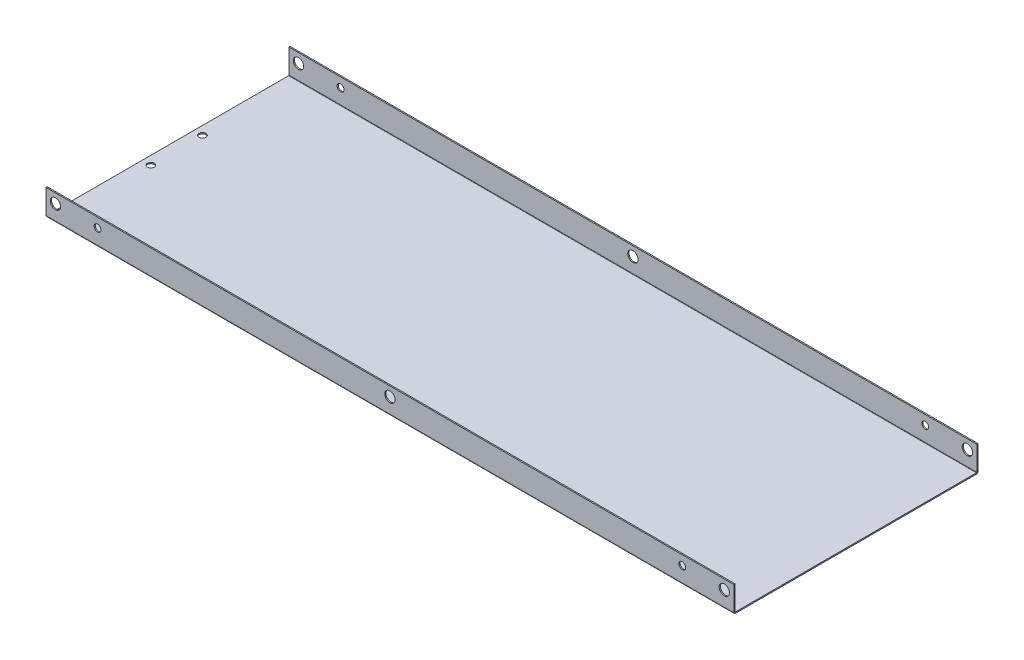
SolidWorks part; units mm, degrees
note: The reader was unsure of these and kept them because the rebuilt part matched: thickness of "基体-法兰1", "边线-法兰1", "钣金8", "钣金9", "钣金10", "钣金11", "钣金12", "钣金13", "钣金14"; flange length of "边线-法兰1".
ref_plane "前视基准面" through (0, 0, 0) normal (0, 0, 1) x (1, 0, 0)
ref_plane "上视基准面" through (0, 0, 0) normal (0, 1, 0) x (1, 0, 0)
ref_plane "右视基准面" through (0, 0, 0) normal (1, 0, 0) x (0, 0, -1)
sketch "草图1" plane through (0, 0, 0) normal (0, 1, 0) x (1, 0, 0)
  line L1 (-200, -71) -> (200, -71)
  line L2 (-200, -71) -> (-200, 71)
  line L3 (-200, 71) -> (200, 71)
  line L4 (200, -71) -> (200, 71)
  line L5 (-200, -71) -> (200, 71) construction
  line L6 (-200, 71) -> (200, -71) construction
  point P0 (0, 0)
  dimension "D1" = 142
  dimension "D2" = 400
base flange "基体-法兰1" sketch "草图1" thickness 0.7 reverse thickness direction no parameters "D1"=0.2
edge flange "边线-法兰1" sketch "草图15" flange profiles "草图15", "草图16" flange angle 90 flange length 15 flange position material inside bend radius 0.2 thickness 0.7 relief rectangular parameters "D6"=10, "D8"=1
sketch "草图15" plane through (0, 0, -71) normal (0, 0, -1) x (-1, 0, 0)
  line L2 (-200, 0) -> (-200, 14.3)
  line L3 (-200, 14.3) -> (200, 14.3)
  line L4 (200, 14.3) -> (200, 0)
  line L11 (-200, 0) -> (200, 0) construction
  line L12 (-200, 0) -> (200, 0)
sketch "草图16" plane through (0, 0, 71) normal (0, 0, 1) x (1, 0, 0)
  line L2 (-200, 0) -> (-200, 14.3)
  line L3 (-200, 14.3) -> (200, 14.3)
  line L4 (200, 14.3) -> (200, 0)
  line L7 (-200, 0) -> (200, 0) construction
  line L8 (-200, 0) -> (200, 0)
bend "边线折弯1" bend radius 0.2 bend angle 90 parameters "D5"=1
bend "边线折弯2" bend radius 0.2 bend angle 90 parameters "D5"=2
sketch "草图17" plane through (0, 0, -71) normal (0, 0, -1) x (-1, 0, 0)
  line L0 (200, 14.3) -> (-200, 14.3) construction
  line L1 (-200, 14.3) -> (-200, 0.2) construction
  line L2 (0, 14.3) -> (0, 0) construction
  circle A0 centre (-194.5, 8.8) radius 3
  circle A1 centre (0, 8.8) radius 3
  circle A2 centre (194.5, 8.8) radius 3
  dimension "D1" = 5.5
  dimension "D2" = 5.5
  dimension "D3" = 6
  dimension "D4" = 5.5
  dimension "D5" = 6
extrude "切除-拉伸1" cut sketch "草图17" against normal blind 10
sketch "草图18" plane through (0, 0, 71) normal (0, 0, 1) x (1, 0, 0)
  line L0 (200, 14.3) -> (-200, 14.3) construction
  line L1 (-200, 14.3) -> (-200, 0.2) construction
  line L2 (0, 14.3) -> (0, 0) construction
  circle A0 centre (-194.5, 8.8) radius 3
  circle A1 centre (0, 8.8) radius 3
  circle A2 centre (194.5, 8.8) radius 3
  dimension "D1" = 5.5
  dimension "D2" = 5.5
  dimension "D3" = 5.5
  dimension "D4" = 6
  dimension "D5" = 6
extrude "切除-拉伸2" cut sketch "草图18" against normal blind 10
sketch "草图19" plane through (0, 0, -71) normal (0, 0, -1) x (-1, 0, 0)
  line L0 (-200, 14.3) -> (-200, 0.2) construction
  line L1 (200, 14.3) -> (-200, 14.3) construction
  line L2 (0, 14.3) -> (0, 0) construction
  circle A0 centre (-170, 8.8) radius 2
  circle A1 centre (170, 8.8) radius 2
  dimension "D2" = 4
  dimension "D3" = 5.5
  dimension "D1" = 30
extrude "切除-拉伸3" cut sketch "草图19" against normal blind 10
sketch "草图20" plane through (0, 0, 71) normal (0, 0, 1) x (1, 0, 0)
  line L0 (-200, 14.3) -> (-200, 0.2) construction
  line L1 (200, 14.3) -> (-200, 14.3) construction
  line L2 (0, 14.3) -> (0, 0) construction
  circle A0 centre (-170, 8.8) radius 2
  circle A1 centre (170, 8.8) radius 2
  dimension "D2" = 4
  dimension "D1" = 30
  dimension "D3" = 5.5
extrude "切除-拉伸4" cut sketch "草图20" against normal blind 10
sketch "草图21" plane through (0, 0, 0) normal (0, 1, 0) x (1, 0, 0)
  line L0 (-200, 0) -> (200, 0) construction
  line L1 (-200, -71) -> (-200, 71) construction
  line L2 (200, -70.1) -> (200, 70.1) construction
  line L3 (-200, 70.1) -> (-200, -70.1) construction
  circle A0 centre (-195, 15) radius 2
  circle A1 centre (-195, -15) radius 2
  dimension "D1" = 4
  dimension "D2" = 15
  dimension "D3" = 5
extrude "切除-拉伸5" cut sketch "草图21" against normal blind 10
sketch "折弯-线3" plane through (0, 0, 0) normal (0, 1, 0) x (1, 0, 0)
sketch "边界框3" plane through (0, 0, 0) normal (0, 1, 0) x (1, 0, 0)
sheet metal parameters "钣金8" thickness 0.7 parameters "D1"=0.2
flat pattern "平板型式8" [suppressed]
sketch "折弯-线4" plane through (0, 0, 0) normal (0, 1, 0) x (1, 0, 0)
sketch "边界框4" [suppressed] plane through (0, 0, 0) normal (0, 1, 0) x (1, 0, 0)
sheet metal parameters "钣金9" thickness 0.7 parameters "D1"=0.2, "D7"=0.01
flat pattern "平板型式8" [suppressed]
sketch "折弯-线4" plane through (0, 0, 0) normal (0, 1, 0) x (1, 0, 0)
sketch "边界框4" [suppressed] plane through (0, 0, 0) normal (0, 1, 0) x (1, 0, 0)
bend of the flat pattern "展平-<边线折弯1>1"
bend of the flat pattern "展平-<边线折弯2>1"
sheet metal parameters "钣金10" thickness 0.7 parameters "D1"=0.2, "D7"=0.01
flat pattern "平板型式8" [suppressed]
sketch "折弯-线4" plane through (0, 0, 0) normal (0, 1, 0) x (1, 0, 0)
sketch "边界框4" [suppressed] plane through (0, 0, 0) normal (0, 1, 0) x (1, 0, 0)
bend of the flat pattern "展平-<边线折弯1>1"
bend of the flat pattern "展平-<边线折弯2>1"
sheet metal parameters "钣金11" thickness 0.7 parameters "D1"=0.2, "D7"=0.01
flat pattern "平板型式8" [suppressed]
sketch "折弯-线4" plane through (0, 0, 0) normal (0, 1, 0) x (1, 0, 0)
sketch "边界框4" [suppressed] plane through (0, 0, 0) normal (0, 1, 0) x (1, 0, 0)
bend of the flat pattern "展平-<边线折弯1>1"
bend of the flat pattern "展平-<边线折弯2>1"
sheet metal parameters "钣金12" thickness 0.7 parameters "D1"=0.2, "D7"=0.01
flat pattern "平板型式8" [suppressed]
sketch "折弯-线4" plane through (0, 0, 0) normal (0, 1, 0) x (1, 0, 0)
sketch "边界框4" [suppressed] plane through (0, 0, 0) normal (0, 1, 0) x (1, 0, 0)
bend of the flat pattern "展平-<边线折弯1>1"
bend of the flat pattern "展平-<边线折弯2>1"
sheet metal parameters "钣金13" thickness 0.7 parameters "D1"=0.2, "D7"=0.01
flat pattern "平板型式8" [suppressed]
sketch "折弯-线4" plane through (0, 0, 0) normal (0, 1, 0) x (1, 0, 0)
sketch "边界框4" [suppressed] plane through (0, 0, 0) normal (0, 1, 0) x (1, 0, 0)
bend of the flat pattern "展平-<边线折弯1>1"
bend of the flat pattern "展平-<边线折弯2>1"
sheet metal parameters "钣金14" thickness 0.7 parameters "D1"=0.2, "D7"=0.01
flat pattern "平板型式8" [suppressed]
sketch "折弯-线4" plane through (0, 0, 0) normal (0, 1, 0) x (1, 0, 0)
sketch "边界框4" [suppressed] plane through (0, 0, 0) normal (0, 1, 0) x (1, 0, 0)
bend of the flat pattern "展平-<边线折弯1>1"
bend of the flat pattern "展平-<边线折弯2>1"
